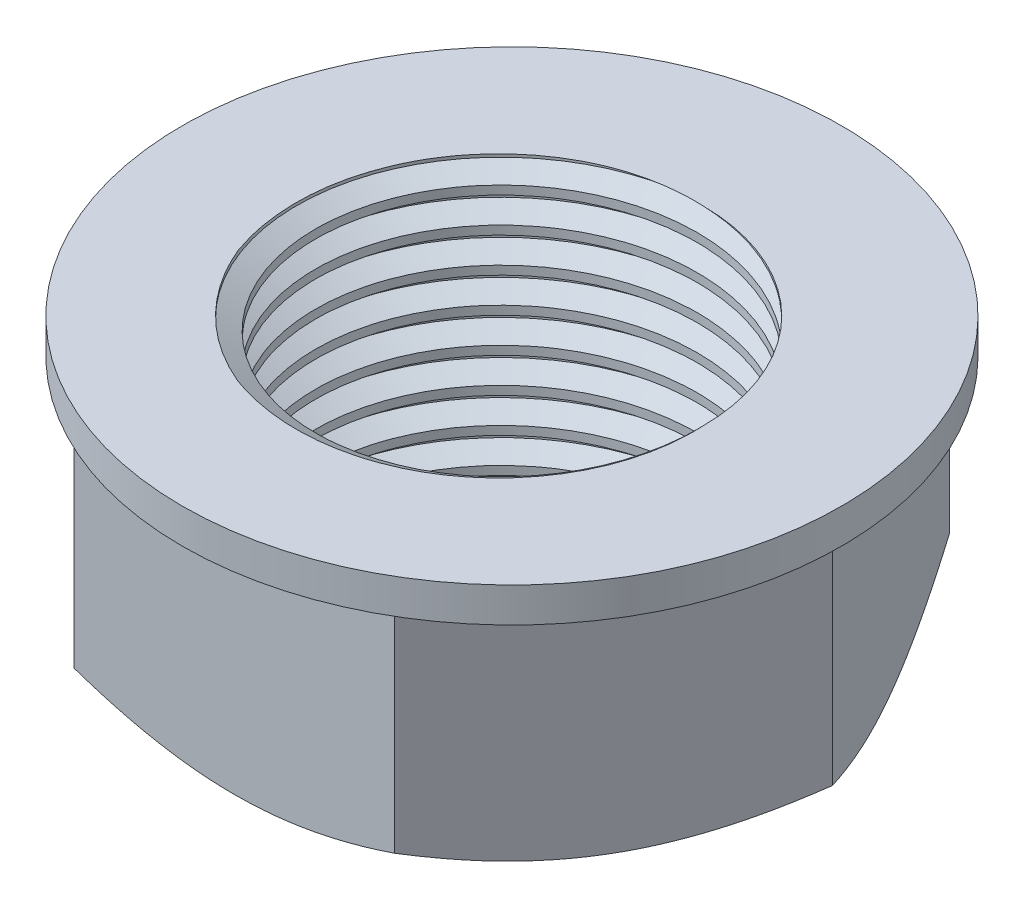
SolidWorks part; units mm, degrees
material "Alloy Steel"
ref_plane "Front Plane" through (0, 0, 0) normal (0, 0, 1) x (1, 0, 0)
ref_plane "Top Plane" through (0, 0, 0) normal (0, 1, 0) x (1, 0, 0)
ref_plane "Right Plane" through (0, 0, 0) normal (1, 0, 0) x (0, 0, -1)
sketch "Sketch6" plane through (0, 0, 0) normal (0, 1, 0) x (1, 0, 0)
  line L1 (18.4752, 0) -> (9.2376, 16)
  line L2 (9.2376, 16) -> (-9.2376, 16)
  line L3 (-9.2376, 16) -> (-18.4752, 0)
  line L4 (-18.4752, 0) -> (-9.2376, -16)
  line L5 (-9.2376, -16) -> (9.2376, -16)
  line L6 (9.2376, -16) -> (18.4752, 0)
  circle A0 centre (0, 0) radius 16 construction
  circle A1 centre (0, 0) radius 11
  dimension "D2" = 22
  dimension "D1" = 32
sketch "Sketch7" plane through (0, 0, 0) normal (0, 0, 1) x (1, 0, 0)
  line L0 (-19.7127, -11.3672) -> (-11.4668, -16.9863)
  line L1 (-11.4668, -16.9863) -> (-19.7127, -16.9863)
  line L2 (-19.7127, -16.9863) -> (-19.7127, -11.3672)
  line L3 (0, -8.1077) -> (0, -21.9154) construction
  point P6 (-19.4873, -9.339)
  point P7 (-19.7127, -11.3672)
extrude "Boss-Extrude3" add sketch "Sketch6" against normal blind 16
revolve "Cut-Revolve3" cut sketch "Sketch7" angle 360 about L3
sketch "Sketch8" plane through (0, 0, 0) normal (0, 1, 0) x (1, 0, 0)
  circle A0 centre (0, 0) radius 19
  circle A1 centre (0, 0) radius 11 construction
  circle A2 centre (0, 0) radius 11
  point P3 (0, 0)
  dimension "D1" = 38
extrude "Boss-Extrude4" add sketch "Sketch8" along normal blind 2
thread "Thread2" pitch 2 method cut profile "Thread Profile2" start angle 0, offset 0, length 0, pitch 2, diameter 22
ref_plane "Plane2" through (11, -16, 0) normal (0, 0, 1) x (1, 0, 0)
sketch "Thread Profile2" plane through (11, -16, 0) normal (0, 0, 1) x (1, 0, 0)
  line L0 (0, 0) -> (0, 2) construction
  line L1 (0, 0) -> (1.0825, 0.625)
  line L2 (1.0825, 0.625) -> (1.0825, 0.875)
  line L3 (1.0825, 0.875) -> (0, 1.5)
  line L4 (1.0825, 0.75) -> (0, 0.75) construction
  line L11 (0, 0) -> (0, 1.5)
  point P2 (0, 0)
  dimension "Pitch" = 2
  dimension "Profile_Angle" = 60
  dimension "Profile_Land" = 0.25
  dimension "Profile_Height" = 1.0825
